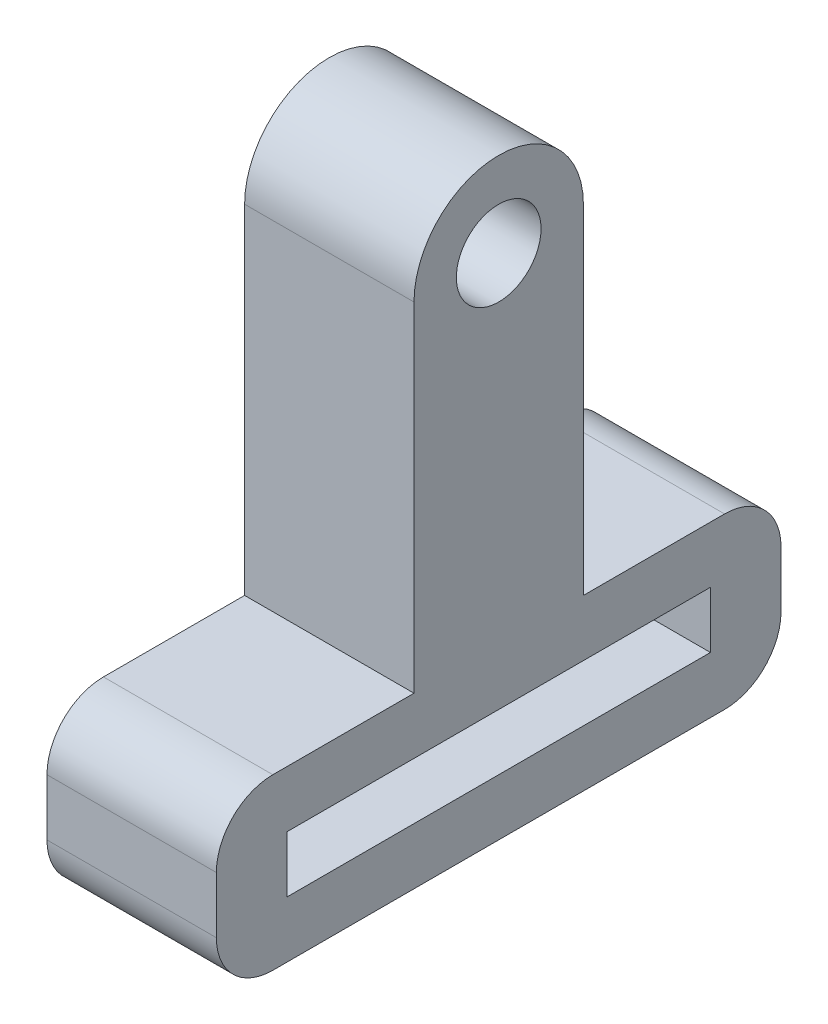
SolidWorks part; units mm, degrees
ref_plane "Alzado" through (0, 0, 0) normal (0, 0, 1) x (1, 0, 0)
ref_plane "Planta" through (0, 0, 0) normal (0, 1, 0) x (1, 0, 0)
ref_plane "Vista lateral" through (0, 0, 0) normal (1, 0, 0) x (0, 0, -1)
sketch "Croquis1" plane through (0, 0, 0) normal (1, 0, 0) x (0, 0, -1)
  line L2 (-10, 1) -> (-10, -1)
  line L3 (-8, -3) -> (8, -3)
  line L4 (10, 1) -> (10, -1)
  line L5 (-10, 3) -> (10, -3) construction
  line L6 (-10, -3) -> (10, 3) construction
  line L7 (-7.5, 1) -> (7.5, 1)
  line L8 (-7.5, 1) -> (-7.5, -1)
  line L9 (-7.5, -1) -> (7.5, -1)
  line L10 (7.5, 1) -> (7.5, -1)
  line L11 (-7.5, 1) -> (7.5, -1) construction
  line L12 (-7.5, -1) -> (7.5, 1) construction
  line L15 (-10, 3) -> (10, 3) construction
  line L27 (-3, 3) -> (-8, 3)
  line L28 (3, 3) -> (8, 3)
  line L35 (0, 3) -> (0, 15) construction
  line L36 (-3, 15) -> (-3, 3)
  line L39 (3, 15) -> (3, 3)
  circle A1 centre (0, 15) radius 1.5
  arc A2 (3, 15) -> (-3, 15) centre (0, 15) ccw
  arc A3 (8, -3) -> (10, -1) centre (8, -1) ccw
  arc A4 (8, 3) -> (10, 1) centre (8, 1) cw
  arc A5 (-10, -1) -> (-8, -3) centre (-8, -1) ccw
  arc A6 (-8, 3) -> (-10, 1) centre (-8, 1) ccw
  point P0 (0, 0)
  point P6 (0, 0)
  dimension "D18" = 6
  dimension "D17" = 3
  dimension "D6" = 2
  dimension "D2" = 20
  dimension "D3" = 2
  dimension "D4" = 15
  dimension "D5" = 6
  dimension "D16" = 12
  dimension "D23" = 2
extrude "Saliente-Extruir1" add sketch "Croquis1" along normal mid plane 6
